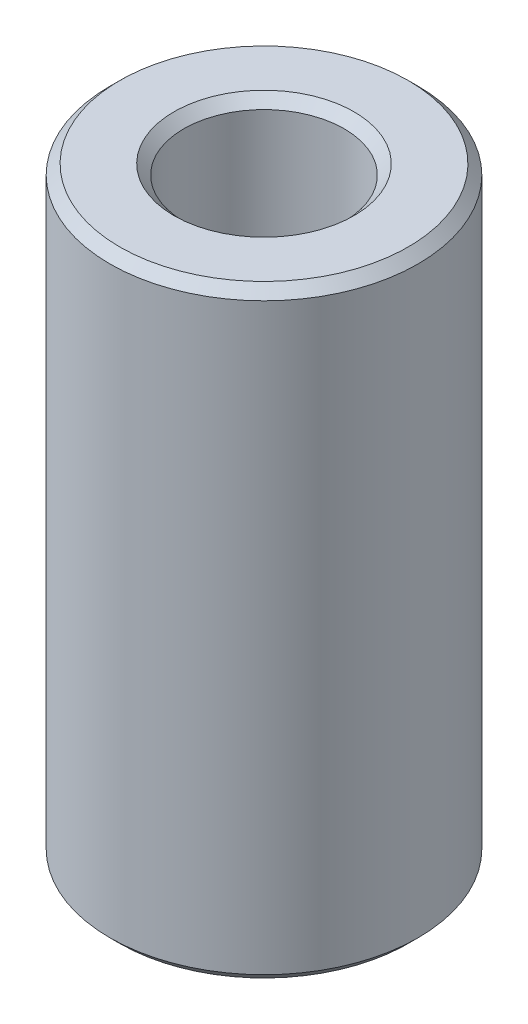
SolidWorks part; units mm, degrees
ref_plane "Front Plane" through (0, 0, 0) normal (0, 0, 1) x (1, 0, 0)
ref_plane "Top Plane" through (0, 0, 0) normal (0, 1, 0) x (1, 0, 0)
ref_plane "Right Plane" through (0, 0, 0) normal (1, 0, 0) x (0, 0, -1)
sketch "Sketch1" plane through (0, 0, 0) normal (0, 1, 0) x (1, 0, 0)
  circle A0 centre (0, 0) radius 5
  dimension "SLEEVE_OD" = 10
extrude "Boss-Extrude1" add sketch "Sketch1" along normal blind 19.5808
sketch "Sketch2" plane through (0, 0, 0) normal (0, 1, 0) x (1, 0, 0)
  circle A0 centre (0, 0) radius 2.604
  dimension "BORE_D" = 5.208
extrude "Cut-Extrude1" cut sketch "Sketch2" along normal through all
chamfer "Chamfer1" distance 0.3187 angle 45 4 edges at (0, 19.5808, 2.604) (0, 0, 2.604) (0, 0, 5) (0, 19.5808, 5)
